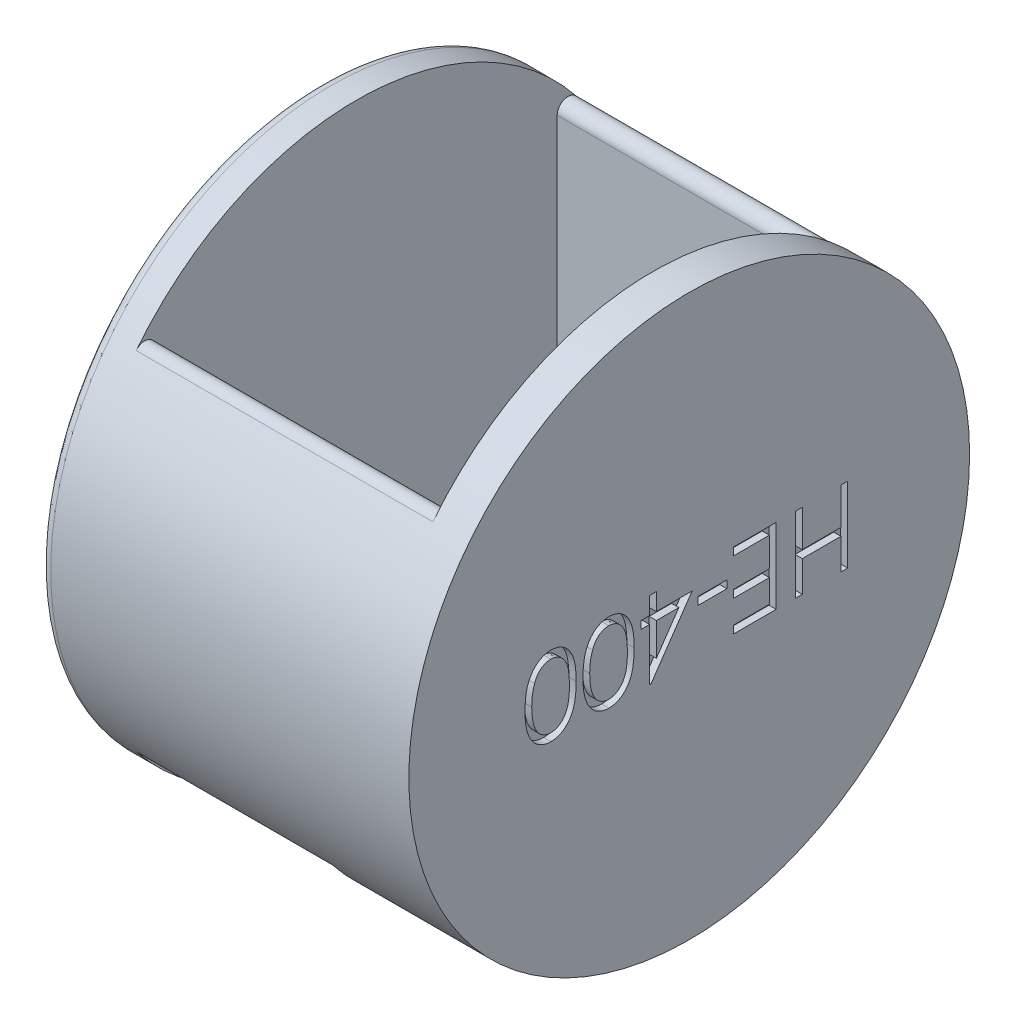
SolidWorks part; units mm, degrees
ref_plane "Front Plane" through (0, 0, 0) normal (0, 0, 1) x (1, 0, 0)
ref_plane "Top Plane" through (0, 0, 0) normal (0, 1, 0) x (1, 0, 0)
ref_plane "Right Plane" through (0, 0, 0) normal (1, 0, 0) x (0, 0, -1)
sketch "Sketch1" plane through (0, 0, 0) normal (1, 0, 0) x (0, 0, -1)
  circle A0 centre (0, 0) radius 14.097
  circle A1 centre (0, 0) radius 19.685
  dimension "D1" = 5.588
  dimension "D2" = 28.194
extrude "Boss-Extrude1" add sketch "Sketch1" along normal blind 2.54 contours A0
extrude "Boss-Extrude2" add sketch "Sketch1<4>" along normal blind 23.368
sketch "Sketch1<4>" plane through (0, 0, 0) normal (1, 0, 0) x (0, 0, -1) same geometry as "Sketch1"
sketch "Sketch2" plane through (23.368, 0, 0) normal (1, 0, 0) x (0, 0, -1)
  circle A0 centre (0, 0) radius 19.685
  dimension "D1" = 39.37
extrude "Boss-Extrude3" add sketch "Sketch2" along normal blind 2.54
ref_plane "Plane1" through (0, 19.685, 0) normal (0, 1, 0) x (1, 0, 0)
sketch "Sketch5" plane through (0, 19.685, 0) normal (0, 1, 0) x (1, 0, 0)
  line L0 (0, -19.685) -> (25.908, -19.685) construction
  line L1 (25.908, -19.685) -> (25.908, 19.685) construction
  line L2 (25.908, 19.685) -> (0, 19.685) construction
  line L3 (0, -19.685) -> (25.908, -19.685)
  line L4 (25.908, -19.685) -> (25.908, 19.685)
  line L5 (25.908, 19.685) -> (0, 19.685)
  line L6 (0, 19.685) -> (0, -19.685) construction
  line L7 (0, 19.685) -> (0, -19.685)
  line L8 (12.954, 19.685) -> (12.954, -19.685) construction
  line L9 (12.954, 14.097) -> (23.368, 14.097)
  line L10 (2.54, 0) -> (12.954, 0) construction
  line L11 (2.54, -19.685) -> (23.368, -19.685)
  line L12 (2.54, -19.685) -> (2.54, 19.685)
  line L13 (2.54, 19.685) -> (23.368, 19.685)
  line L14 (23.368, -19.685) -> (23.368, 19.685)
  line L15 (2.54, -19.685) -> (23.368, 19.685) construction
  line L16 (2.54, 19.685) -> (23.368, -19.685) construction
  line L17 (2.54, -14.097) -> (12.954, -14.097)
  line L18 (2.54, -14.097) -> (2.54, 14.097)
  line L19 (2.54, 14.097) -> (12.954, 14.097)
  line L20 (12.954, -14.097) -> (12.954, 14.097)
  line L21 (2.54, -14.097) -> (12.954, 14.097) construction
  line L22 (2.54, 14.097) -> (12.954, -14.097) construction
  line L23 (12.954, -14.097) -> (23.368, -14.097)
  line L24 (16.256, 14.097) -> (16.256, -14.097)
  point P6 (7.747, 0)
  point P8 (12.954, 0)
  dimension "D1" = 2.54
  dimension "D2" = 5.588
  dimension "D3" = 7.112
  dimension "D4" = 5.588
extrude "Cut-Extrude14" cut sketch "Sketch5" against normal through all both and the other way through all contours L17 L20 L19 L12 | L24 L9 L20 L23 region at (7.747, 19.685, 0) region at (14.605, 19.685, 0)
extrude "Cut-Extrude15" cut sketch "Sketch5<7>" against normal blind 19.685 contours L20 L23 L14 L9 region at (19.812, 19.685, 0)
sketch "Sketch5<7>" plane through (0, 19.685, 0) normal (0, 1, 0) x (1, 0, 0) same geometry as "Sketch5"
sketch "Sketch6" plane through (25.908, 0, 0) normal (1, 0, 0) x (0, 0, -1)
  line L0 (0, 19.685) -> (0, -19.685) construction
  line L1 (14.2494, 19.685) -> (-14.2494, 19.685) construction
  line L2 (-19.685, 0) -> (19.685, 0) construction
  line L4 (-19.5064, 2.6458) -> (19.5064, 2.6458) construction
  circle A0 centre (0, 0) radius 19.685 construction
  text T0 "HE-400" font "Century Gothic" height 5.2917
  dimension "D1" = 2.6458
extrude "Cut-Extrude16" cut sketch "Sketch6" against normal blind 0.508
fillet "Fillet1" radius 0.762 5 edges at (12.954, 13.7395, -14.097) (12.954, 13.7395, 14.097) (9.398, -13.7395, 14.097) (9.398, -13.7395, -14.097) (0, 0, -19.685)
